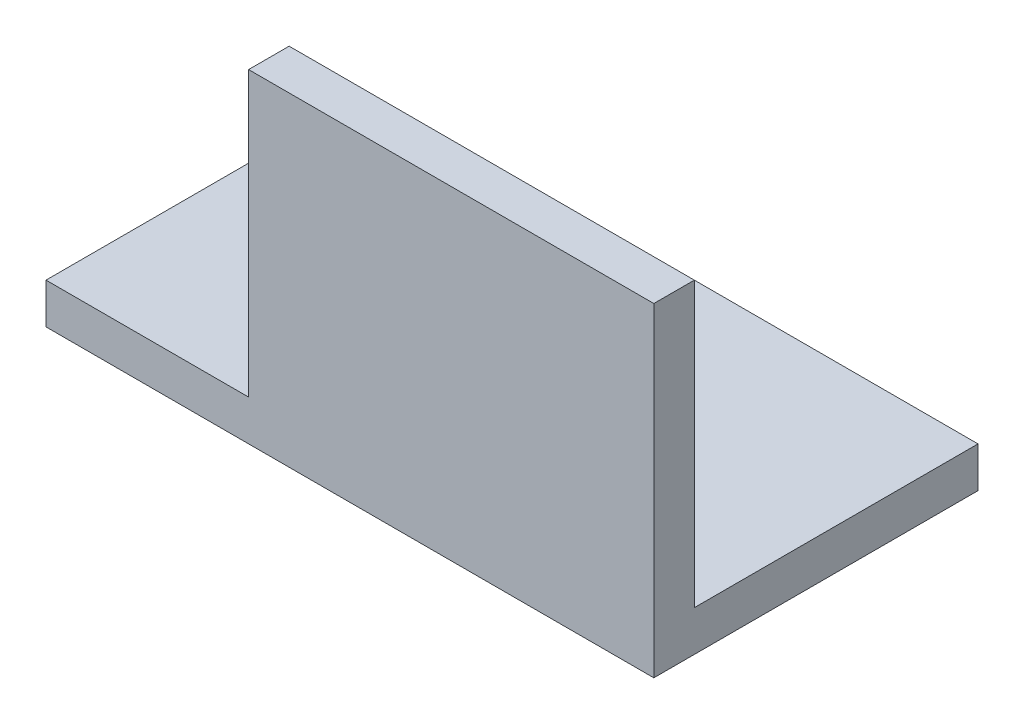
SolidWorks part; units mm, degrees
ref_plane "Спереди" through (0, 0, 0) normal (0, 0, 1) x (1, 0, 0)
ref_plane "Сверху" through (0, 0, 0) normal (0, 1, 0) x (1, 0, 0)
ref_plane "Справа" through (0, 0, 0) normal (1, 0, 0) x (0, 0, -1)
sketch "Эскиз1" plane through (0, 0, 0) normal (1, 0, 0) x (0, 0, -1)
  line L0 (0, 0) -> (32, 0)
  line L1 (0, 0) -> (0, 32)
extrude "Вытянуть-Тонкостенный1" add sketch "Эскиз1" along normal blind 60 thin thin type one direction wall 4
sketch "Эскиз2" plane through (0, 0, 0) normal (0, 0, 1) x (1, 0, 0)
  line L1 (0, 32) -> (20, 32)
  line L2 (0, 32) -> (0, 4)
  line L3 (0, 4) -> (20, 4)
  line L4 (20, 32) -> (20, 4)
extrude "Вырез-Вытянуть1" cut sketch "Эскиз2" against normal through all
